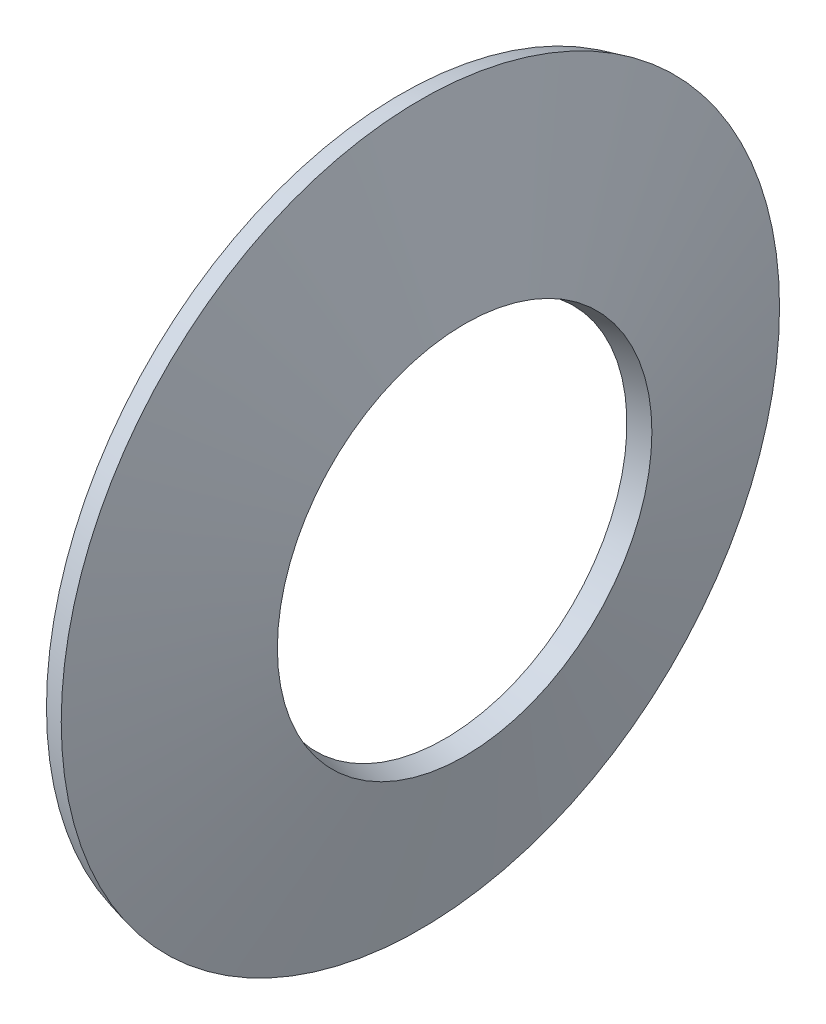
SolidWorks part; units mm, degrees
ref_plane "Plan1" through (0, 0, 0) normal (0, 0, 1) x (1, 0, 0)
ref_plane "Plan2" through (0, 0, 0) normal (0, 1, 0) x (1, 0, 0)
ref_plane "Plan3" through (0, 0, 0) normal (1, 0, 0) x (0, 0, -1)
sketch "Esquisse2" plane through (0, 0, 0) normal (0, 0, 1) x (1, 0, 0)
  line L0 (1.7253, 7.1) -> (2.5, 7.2995) construction
  line L1 (2.5, 7.2995) -> (0.7747, 14) construction
  line L2 (0.7747, 14) -> (0, 13.8005) construction
  line L3 (0, 13.8005) -> (1.7253, 7.1) construction
  line L4 (1.7253, 7.1) -> (2.5, 7.2995)
  line L5 (2.5, 7.2995) -> (0.7747, 14)
  line L6 (0.7747, 14) -> (0, 13.8005)
  line L7 (0, 13.8005) -> (1.7253, 7.1)
  line L8 (0, 0) -> (2.5, 0) construction
  line L9 (0, 0) -> (2.5, 0) construction
  line L10 (2.5, 7.2995) -> (4.3795, 0) construction
  line L11 (1.7253, 7.1) -> (3.5534, 0) construction
revolve "Base-Révolution" add sketch "Esquisse2" angle 360 about L8
ref_plane "Plan4" through (2.5, 0, 0) normal (1, 0, 0) x (0, 0, -1)
ref_axis "Axe1" through (-50, 0, 0) along (1, 0, 0)
